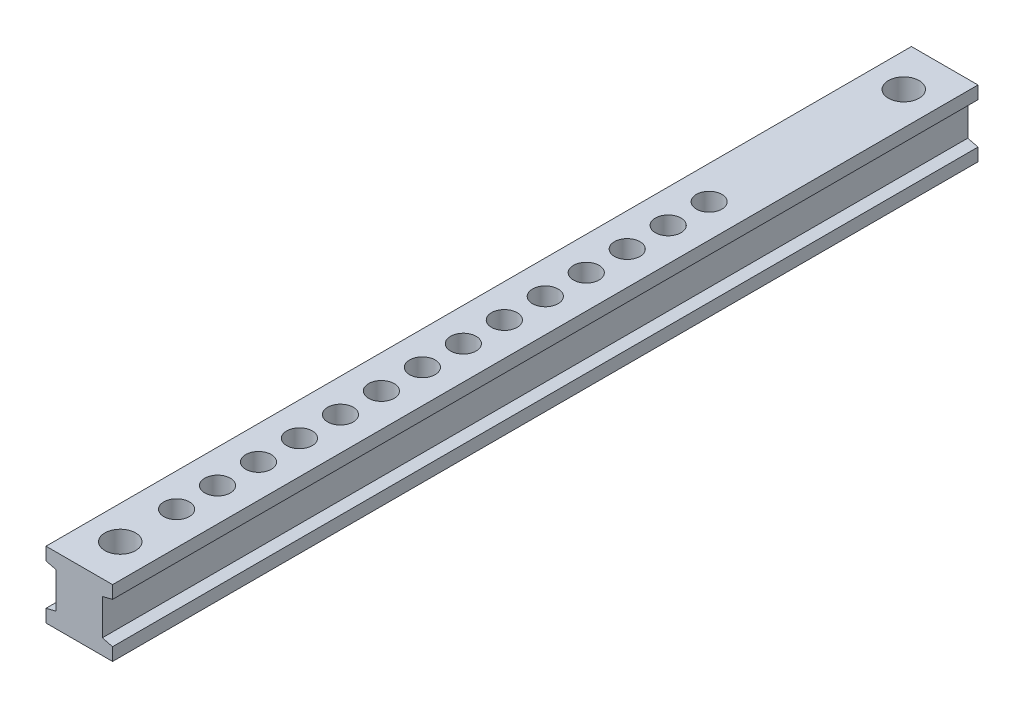
SolidWorks part; units mm, degrees
ref_plane "Front Plane" through (0, 0, 0) normal (0, 0, 1) x (1, 0, 0)
ref_plane "Top Plane" through (0, 0, 0) normal (0, 1, 0) x (1, 0, 0)
ref_plane "Right Plane" through (0, 0, 0) normal (1, 0, 0) x (0, 0, -1)
sketch "Sketch1" plane through (0, 0, 0) normal (0, 0, 1) x (1, 0, 0)
  line L0 (6.5, 4) -> (4.5, 3.5)
  line L1 (-6.5, 6.5) -> (6.5, 6.5)
  line L2 (-6.5, 6.5) -> (-6.5, -6.5)
  line L3 (-6.5, -6.5) -> (6.5, -6.5)
  line L4 (6.5, 6.5) -> (6.5, -6.5)
  line L5 (-6.5, 6.5) -> (6.5, -6.5) construction
  line L6 (-6.5, -6.5) -> (6.5, 6.5) construction
  line L7 (4.5, 3.5) -> (4.5, -3.5)
  line L8 (4.5, -3.5) -> (6.5, -4)
  line L9 (-4.5, 0) -> (4.5, 0) construction
  line L10 (0, -6.5) -> (0, 6.5) construction
  line L11 (6.5, -6.5) -> (-6.5, 6.5) construction
  line L12 (6.5, 6.5) -> (-6.5, -6.5) construction
  line L13 (-4.5, -3.5) -> (-6.5, -4)
  line L14 (-4.5, 3.5) -> (-4.5, -3.5)
  line L15 (-6.5, 6.5) -> (-6.5, -6.5)
  line L16 (-6.5, 4) -> (-4.5, 3.5)
  point P0 (0, 0)
  point P13 (0, 0)
  dimension "D1" = 13
  dimension "D2" = 13
  dimension "D3" = 7
  dimension "D4" = 2
  dimension "D5" = 8
extrude "Boss-Extrude1" add sketch "Sketch1" along normal mid plane 169 contours L2 L16 L14 L13 L3 L4 L8 L7 L0 L1 region at (0, 0, 0)
sketch "Sketch2" plane through (0, 0, 0) normal (0, 1, 0) x (1, 0, 0)
  line L0 (0, 84.5) -> (0, -84.5) construction
  line L1 (-6.5, 84.5) -> (6.5, 84.5) construction
  line L2 (-6.5, -84.5) -> (6.5, -84.5) construction
  line L3 (0, -65.5) -> (0, -57.5) construction
  circle A0 centre (0, 76.5) radius 3
  circle A1 centre (0, -76.5) radius 3
  circle A2 centre (0, -65.5) radius 2.5
  circle A3 centre (0, -57.5) radius 2.5
  circle A4 centre (0, -49.5) radius 2.5
  circle A5 centre (0, -41.5) radius 2.5
  circle A6 centre (0, -33.5) radius 2.5
  circle A7 centre (0, -25.5) radius 2.5
  circle A8 centre (0, -17.5) radius 2.5
  circle A9 centre (0, -9.5) radius 2.5
  circle A10 centre (0, -1.5) radius 2.5
  circle A11 centre (0, 6.5) radius 2.5
  circle A12 centre (0, 14.5) radius 2.5
  circle A13 centre (0, 22.5) radius 2.5
  circle A14 centre (0, 30.5) radius 2.5
  circle A15 centre (0, 38.5) radius 2.5
  point P12 (0, 0)
  point P41 (0, 0)
  point P42 (0, 0)
  point P43 (0, 0)
  dimension "D2" = 6
  dimension "D4" = 5
  dimension "D1" = 8
  dimension "D3" = 8
  dimension "D5" = 19
  dimension "D7" = 8
  dimension "D6" = 14
extrude "Cut-Extrude1" cut sketch "Sketch2" against normal through all both and the other way through all
equation "\"D3@Sketch2\"=\"D1@Sketch2\""
